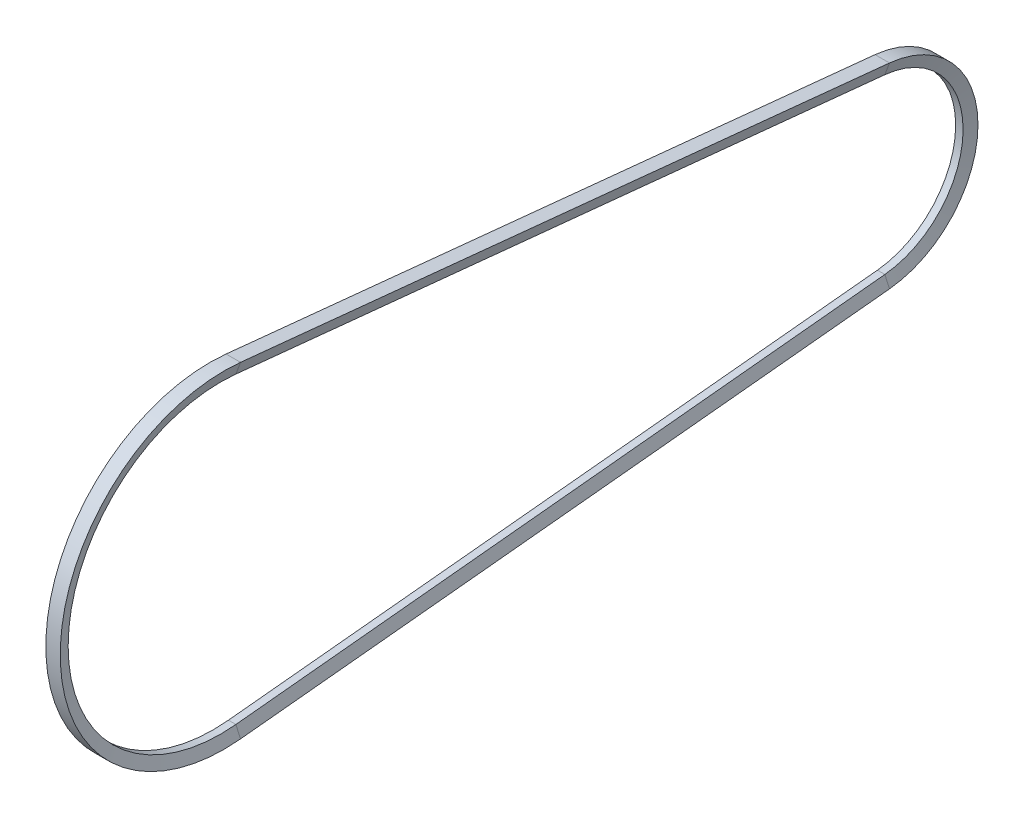
SolidWorks part; units mm, degrees
ref_plane "前视基准面" through (0, 0, 0) normal (0, 0, 1) x (1, 0, 0)
ref_plane "上视基准面" through (0, 0, 0) normal (0, 1, 0) x (1, 0, 0)
ref_plane "右视基准面" through (0, 0, 0) normal (1, 0, 0) x (0, 0, -1)
sketch "草图1" plane through (0, 0, 0) normal (1, 0, 0) x (0, 0, -1)
  line L0 (12.5, 124.3734) -> (507.5, 74.6241)
  line L1 (12.5, -124.3734) -> (507.5, -74.6241)
  line L2 (0, 0) -> (500, 0) construction
  arc A0 (12.5, 124.3734) -> (12.5, -124.3734) centre (0, 0) ccw
  arc A1 (507.5, -74.6241) -> (507.5, 74.6241) centre (500, 0) ccw
  dimension "D1" = 125
  dimension "D2" = 75
  dimension "D3" = 500
sketch "草图2" plane through (0, 0, 0) normal (0, 0, 1) x (1, 0, 0)
  line L0 (-5.5, 125) -> (5.5, 125)
  line L1 (5.5, 125) -> (2.8401, 116.3)
  line L2 (2.8401, 116.3) -> (-2.8401, 116.3)
  line L3 (-2.8401, 116.3) -> (-5.5, 125)
  line L4 (0, 116.3) -> (0, 125) construction
  line L5 (0, -125) -> (0, 125) construction
  dimension "D1" = 11
  dimension "D2" = 8.7
  dimension "D3" = 34
sweep "扫描1" add profiles "草图2" path "草图1"
equation "\"D3@草图1\" = \"D1@距离1@辐板轮_辐板轮.Assembly\""
equation "\"D1@草图2\" = \"bd@草图1@大带轮_辐板轮.Part\" "
equation "\"D2@草图2\" = \"hf@草图1@大带轮_辐板轮.Part\" "
equation "\"D3@草图2\" = \"槽轮角@草图1@大带轮_辐板轮.Part\" "
equation "\"D2@草图1\" = \"dd@草图1@小带轮_辐板轮.Part\"/2  "
equation "\"D1@草图1\" = \"dd@草图1@大带轮_辐板轮.Part\" /2"
